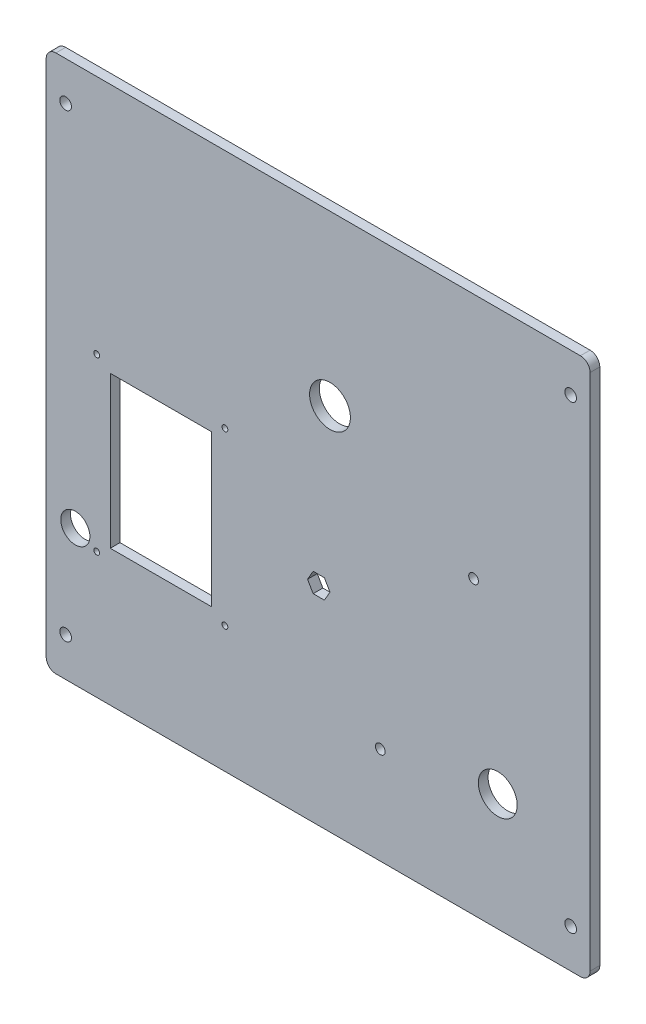
SolidWorks part; units mm, degrees
ref_plane "Plan de face" through (0, 0, 0) normal (0, 0, 1) x (1, 0, 0)
ref_plane "Plan de dessus" through (0, 0, 0) normal (0, 1, 0) x (1, 0, 0)
ref_plane "Plan de droite" through (0, 0, 0) normal (1, 0, 0) x (0, 0, -1)
sketch "Esquisse1" plane through (0, 0, 0) normal (0, 0, 1) x (1, 0, 0)
  line L1 (0, 0) -> (280, 0)
  line L2 (0, 0) -> (0, 276.83)
  line L3 (0, 276.83) -> (280, 276.83)
  line L4 (280, 0) -> (280, 276.83)
  dimension "D1" = 276.83
  dimension "D2" = 280
extrude "Boss.-Extru.1" add sketch "Esquisse1" along normal blind 5
sketch "Esquisse2" plane through (0, 0, 0) normal (0, 0, 1) x (1, 0, 0)
  line L1 (85, 148) -> (33, 148)
  line L2 (0, 0) -> (280, 0) construction
  line L3 (0, 0) -> (0, 276.83) construction
  line L4 (0, 276.83) -> (280, 276.83) construction
  line L5 (280, 0) -> (280, 276.83) construction
  line L6 (85, 148) -> (85, 70)
  line L7 (137.4335, 111.9714) -> (134.5467, 106.9714)
  line L8 (134.5467, 106.9714) -> (137.4335, 101.9714)
  line L9 (137.4335, 101.9714) -> (143.207, 101.9714)
  line L10 (143.207, 101.9714) -> (146.0937, 106.9714)
  line L11 (146.0937, 106.9714) -> (143.207, 111.9714)
  line L12 (143.207, 111.9714) -> (137.4335, 111.9714)
  line L13 (85, 70) -> (33, 70)
  line L14 (33, 148) -> (33, 70)
  circle A0 centre (270, 256.83) radius 3
  circle A1 centre (10, 256.83) radius 3
  circle A2 centre (10, 20) radius 3
  circle A3 centre (270, 20) radius 3
  circle A4 centre (140.3202, 106.9714) radius 5 construction
  circle A5 centre (220, 150) radius 2.5
  circle A6 centre (172, 50) radius 2.5
  circle A7 centre (92, 153) radius 1.5
  circle A8 centre (26, 153) radius 1.5
  circle A9 centre (92, 65) radius 1.5
  circle A10 centre (26, 65) radius 1.5
  circle A11 centre (15, 70) radius 7.5
  circle A12 centre (146.0937, 190) radius 10.5
  circle A13 centre (232.4771, 60.1974) radius 10
  dimension "D1" = 6
  dimension "D2" = 6
  dimension "D3" = 6
  dimension "D4" = 6
  dimension "D5" = 20
  dimension "D6" = 10
  dimension "D7" = 20
  dimension "D8" = 10
  dimension "D9" = 10
  dimension "D10" = 20
  dimension "D11" = 10
  dimension "D12" = 20
  dimension "D13" = 10
  dimension "D14" = 100
  dimension "D15" = 48
  dimension "D16" = 5
  dimension "D17" = 5
  dimension "D19" = 50
  dimension "D26" = 7
  dimension "D27" = 5
  dimension "D29" = 7
  dimension "D30" = 5
  dimension "D32" = 3
  dimension "D33" = 3
  dimension "D34" = 3
  dimension "D35" = 3
  dimension "D38" = 15
  dimension "D39" = 21
  dimension "D40" = 20
  dimension "D18" = 60
  dimension "D20" = 52
  dimension "D21" = 78
  dimension "D22" = 70
  dimension "D23" = 85
  dimension "D24" = 5
  dimension "D25" = 7
  dimension "D28" = 5
  dimension "D31" = 7
  dimension "D36" = 18
extrude "Enlèv. mat.-Extru.1" cut sketch "Esquisse2" along normal through all
fillet "Congé1" radius 5 4 edges at (280, 276.83, 2.5) (280, 0, 2.5) (0, 0, 2.5) (0, 276.83, 2.5)
